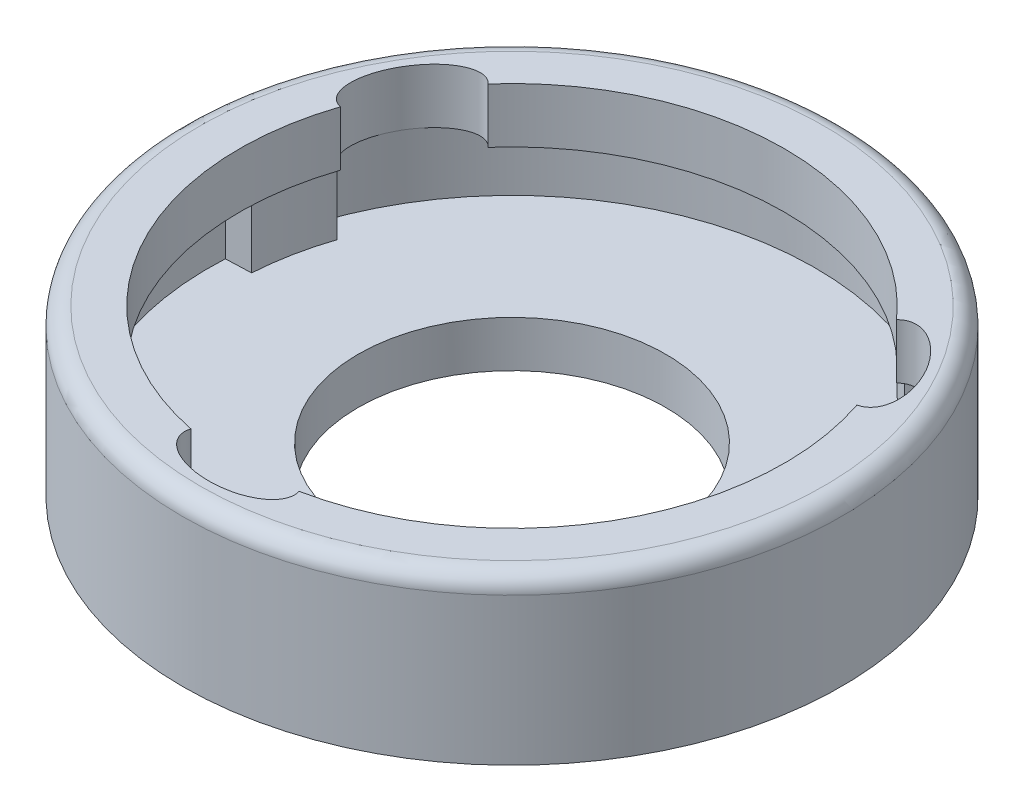
SolidWorks part; units mm, degrees
ref_plane "Ebene vorne" through (0, 0, 0) normal (0, 0, 1) x (1, 0, 0)
ref_plane "Ebene oben" through (0, 0, 0) normal (0, 1, 0) x (1, 0, 0)
ref_plane "Ebene rechts" through (0, 0, 0) normal (1, 0, 0) x (0, 0, -1)
sketch "Skizze1" plane through (0, 0, 0) normal (0, 1, 0) x (1, 0, 0)
  circle A0 centre (0, 0) radius 7.5
  circle A3 centre (0, 0) radius 3.5
extrude "Aufsatz-Linear austragen2" add sketch "Skizze1" along normal blind 0.8
sketch "Skizze5" plane through (0, 0.8, 0) normal (0, 1, 0) x (1, 0, 0)
  circle A0 centre (0, 0) radius 6.9
  circle A1 centre (0, 0) radius 7.5
extrude "Aufsatz-Linear austragen4" add sketch "Skizze5" along normal blind 1.7
sketch "Skizze18" plane through (0, 2.5, 0) normal (0, 1, 0) x (1, 0, 0)
  circle A0 centre (0, 0) radius 7.5
  circle A1 centre (0, 0) radius 6.2
extrude "Aufsatz-Linear austragen5" add sketch "Skizze18" along normal blind 1.25
sketch "Skizze19" plane through (0, 3.75, 0) normal (0, 1, 0) x (1, 0, 0)
  ellipse E1 centre (0, -6.2) end of major axis (-1.25, -6.2) minor radius 0.7
extrude "Schnitt-Linear austragen1" cut sketch "Skizze19" against normal blind 1.75
sketch "Skizze21" plane through (0, 0.8, 0) normal (0, 1, 0) x (1, 0, 0)
  line L5 (1.25, -6.2) -> (1.5834, -7.331)
  line L6 (2.8203, -5.6611) -> (3.4483, -6.6603)
  arc A9 (1.5834, -7.331) -> (3.4483, -6.6603) centre (0, 0) ccw
  circle A10 centre (0, 0) radius 7.5 construction
  arc A11 (1.25, -6.2) -> (2.8203, -5.6611) centre (0, 0) ccw
  ellipse E0 centre (0, -6.2) end of major axis (-1.25, -6.2) minor radius 0.7 (-1.2304, -6.0767) -> (1.2304, -6.0767) ccw construction
extrude "Aufsatz-Linear austragen6" add sketch "Skizze21" along normal blind 1.7
sketch "Skizze22" plane through (0, 0.8, 0) normal (0, 1, 0) x (1, 0, 0)
  line L2 (1.1618, -3.3015) -> (2.2905, -6.5087)
  line L3 (-1.1618, -3.3015) -> (-2.2905, -6.5087)
  arc A0 (-2.2905, -6.5087) -> (2.2905, -6.5087) centre (0, 0) cw
  arc A1 (3.1278, -6.1503) -> (1.4132, -6.7537) centre (0, 0) ccw construction
  arc A2 (-1.1618, -3.3015) -> (1.1618, -3.3015) centre (0, 0) cw
  circle A3 centre (0, 0) radius 3.5 construction
  arc A4 (3.1278, -6.1503) -> (1.4132, -6.7537) centre (0, 0) ccw construction
extrude "Aufsatz-Linear austragen7" add sketch "Skizze22" along normal blind 0.25
pattern_circular "Kreismuster2" count 3 over 360 about axis through (0, 3.75, 0) along (0, -1, 0) of "Schnitt-Linear austragen1"
pattern_circular "Kreismuster4" count 3 over 360 about axis through (0, 2.5, 0) along (0, -1, 0) of "Aufsatz-Linear austragen6" reverse direction yes
fillet "Verrundung1" radius 0.4 1 edges at (0, 3.75, 7.5)
